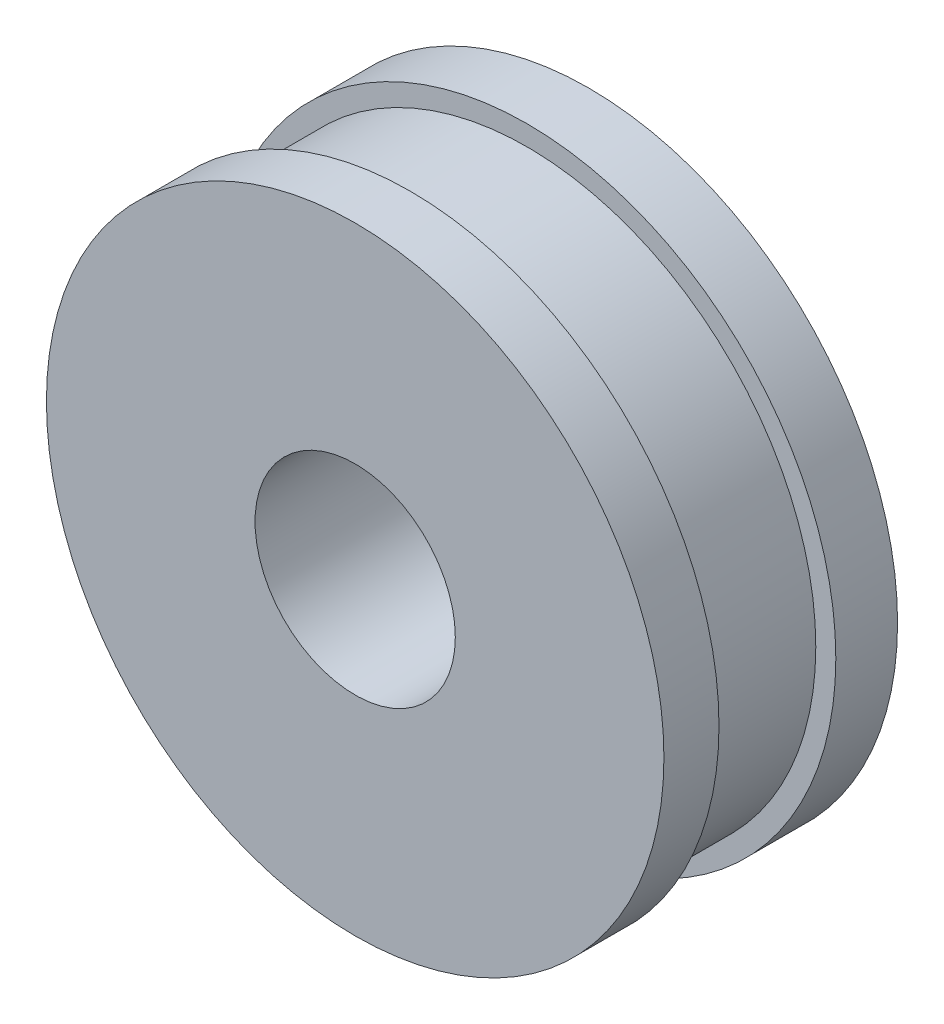
SolidWorks part; units mm, degrees
ref_plane "前视基准面" through (0, 0, 0) normal (0, 0, 1) x (1, 0, 0)
ref_plane "上视基准面" through (0, 0, 0) normal (0, 1, 0) x (1, 0, 0)
ref_plane "右视基准面" through (0, 0, 0) normal (1, 0, 0) x (0, 0, -1)
sketch "草图1" plane through (0, 0, 0) normal (0, 0, 1) x (1, 0, 0)
  circle A0 centre (0, 0) radius 18.5
  circle A2 centre (0, 0) radius 6
  dimension "D1" = 12
extrude "凸台-拉伸1" add sketch "草图1" along normal blind 14
ref_plane "基准面4" through (0, 0, 7.7) normal (0, 0, 1) x (1, 0, 0)
sketch "草图2" plane through (0, 0, 7.7) normal (0, 0, 1) x (1, 0, 0)
  circle A0 centre (0, 0) radius 17.3
  circle A1 centre (0, 0) radius 18.5
extrude "切除-拉伸1" cut sketch "草图2" against normal blind 2.2
extrude "切除-拉伸2" cut sketch "草图2<2>" along normal blind 0.8
sketch "草图2<2>" plane through (0, 0, 7.7) normal (0, 0, 1) x (1, 0, 0) same geometry as "草图2"
extrude "切除-拉伸3" cut sketch "草图2<4>" against normal blind 4
sketch "草图2<4>" plane through (0, 0, 7.7) normal (0, 0, 1) x (1, 0, 0) same geometry as "草图2"
extrude "切除-拉伸5" cut sketch "草图2<6>" along normal blind 3
sketch "草图2<6>" plane through (0, 0, 7.7) normal (0, 0, 1) x (1, 0, 0) same geometry as "草图2"
